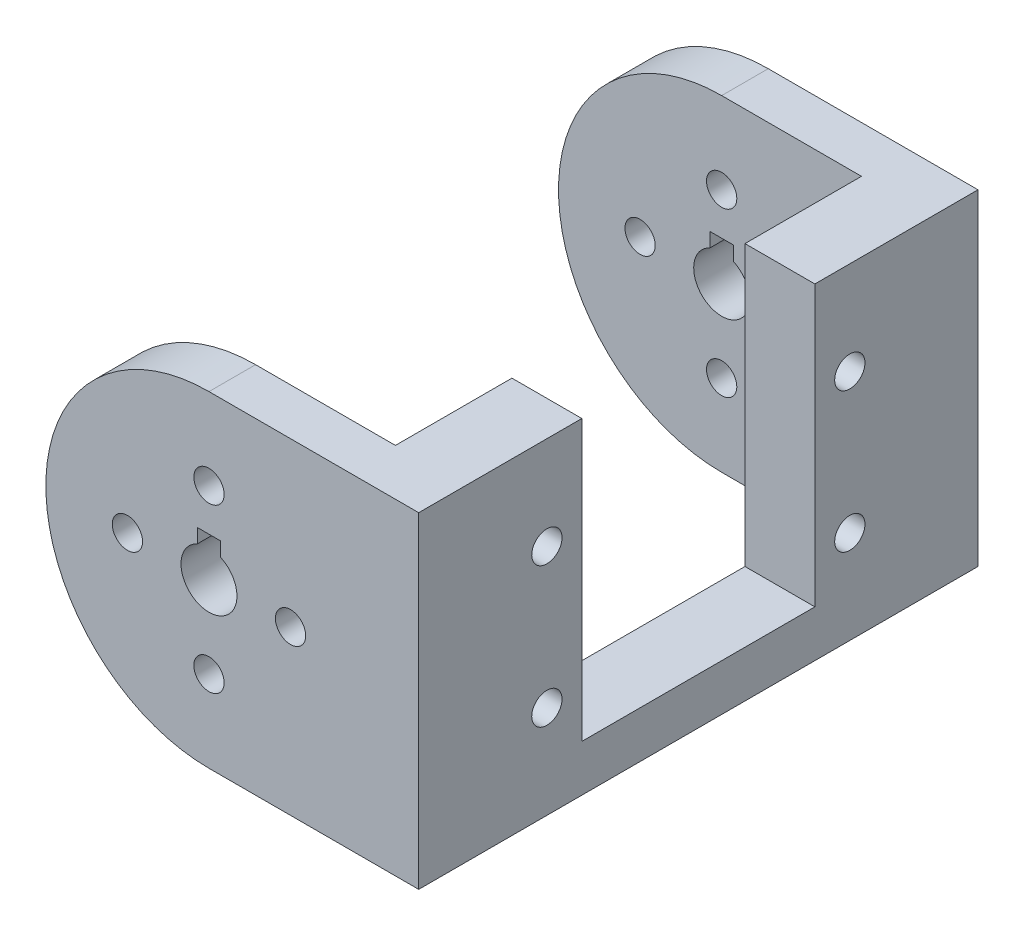
SolidWorks part; units mm, degrees
ref_plane "Alzado" through (0, 0, 0) normal (0, 0, 1) x (1, 0, 0)
ref_plane "Planta" through (0, 0, 0) normal (0, 1, 0) x (1, 0, 0)
ref_plane "Vista lateral" through (0, 0, 0) normal (1, 0, 0) x (0, 0, -1)
sketch "Sketch1" plane through (0, 0, 0) normal (0, 1, 0) x (1, 0, 0)
  line L0 (-40, -50) -> (25, -50)
  line L1 (-40, 60) -> (40, 60)
  line L2 (-40, 60) -> (-40, -60)
  line L3 (-40, -60) -> (40, -60)
  line L4 (40, 60) -> (40, -60)
  line L5 (-40, 60) -> (40, -60) construction
  line L6 (-40, -60) -> (40, 60) construction
  line L7 (25, -50) -> (25, 50)
  line L8 (25, 50) -> (-40, 50)
  point P0 (0, 0)
  dimension "D1" = 120
  dimension "D2" = 10
  dimension "D3" = 10
  dimension "D4" = 80
  dimension "D5" = 15
  dimension "D6" = 100
extrude "Boss-Extrude1" add sketch "Sketch1" along normal mid plane 70 contours L8 L7 L0 L2 L3 L4 L1 region at (-7.5, 0, 51.4422)
fillet "Fillet1" 2 edges at (-40, 35, 55) (-40, -35, 55) type full round first side face at (-3.75, 35, 0) second side face at (-3.75, -35, 0) middle face at (-40, 0, 55)
fillet "Fillet2" 2 edges at (-40, -35, -55) (-40, 35, -55) type full round first side face at (5, -35, 0) second side face at (5, 35, 0) middle face at (-40, 0, -55)
sketch "Sketch2" plane through (0, 0, 60) normal (0, 0, 1) x (1, 0, 0)
  line L5 (-7.5, 8.5) -> (-2.5, 8.5)
  line L6 (-7.5, 8.5) -> (-7.5, 3.5)
  line L7 (-7.5, 3.5) -> (-2.5, 3.5)
  line L8 (-2.5, 8.5) -> (-2.5, 3.5)
  line L9 (-7.5, 8.5) -> (-2.5, 3.5) construction
  line L10 (-7.5, 3.5) -> (-2.5, 8.5) construction
  circle A0 centre (-5, 0) radius 6
  arc A1 (-5, 35) -> (-5, -35) centre (-5, 0) ccw construction
  point P1 (-5, 6)
  point P2 (-5, 6)
  dimension "D1" = 12
  dimension "D2" = 5
extrude "Cut-Extrude1" cut sketch "Sketch2" against normal through all contours A0 L8 L5 L6 | L8 A0 L6 L7 | L6 A0 L8 L7 region at (-5, 7.1559, 60) region at (-5, 4.6664, 60) region at (-5, -0.5337, 60)
sketch "Sketch4" plane through (0, 0, 60) normal (0, 0, 1) x (1, 0, 0)
  circle A0 centre (-5, 0) radius 17.5 construction
  circle A1 centre (-5, 17.5) radius 3.25
  dimension "D1" = 35
  dimension "D2" = 6.5
extrude "Cut-Extrude2" cut sketch "Sketch4" against normal through all
pattern_circular "CirPattern1" count 4 over 360 about axis through (-5, 0, -60) along (0, 0, 1) of "Cut-Extrude2" reverse direction yes
sketch "Sketch5" plane through (40, 0, 0) normal (1, 0, 0) x (0, 0, -1)
  line L0 (-25, 25) -> (-25, 35)
  line L2 (-25, 25) -> (-25, -25)
  line L3 (-25, -25) -> (25, -25)
  line L4 (25, 25) -> (25, -25)
  line L5 (-25, 25) -> (25, -25) construction
  line L6 (-25, -25) -> (25, 25) construction
  line L7 (60, 35) -> (-60, 35) construction
  line L9 (25, 35) -> (-25, 35)
  line L10 (25, 35) -> (25, 25)
  point P0 (0, 0)
  dimension "D1" = 50
  dimension "D2" = 10
extrude "Cut-Extrude3" cut sketch "Sketch5" against normal through all
sketch "Sketch6" plane through (25, 0, 0) normal (-1, 0, 0) x (0, 0, 1)
  line L2 (-32.5, 15) -> (32.5, 15) construction
  line L3 (-32.5, 15) -> (-32.5, -15) construction
  line L5 (-32.5, -15) -> (32.5, -15) construction
  line L6 (32.5, 15) -> (32.5, -15) construction
  line L7 (-32.5, 15) -> (32.5, -15) construction
  line L8 (-32.5, -15) -> (32.5, 15) construction
  circle A0 centre (-32.5, 15) radius 3.25
  circle A1 centre (-32.5, -15) radius 3.25
  circle A2 centre (32.5, -15) radius 3.25
  circle A3 centre (32.5, 15) radius 3.25
  point P0 (0, 0)
  dimension "D3" = 6.5
  dimension "D1" = 30
  dimension "D2" = 65
extrude "Cut-Extrude4" cut sketch "Sketch6" against normal blind 23
